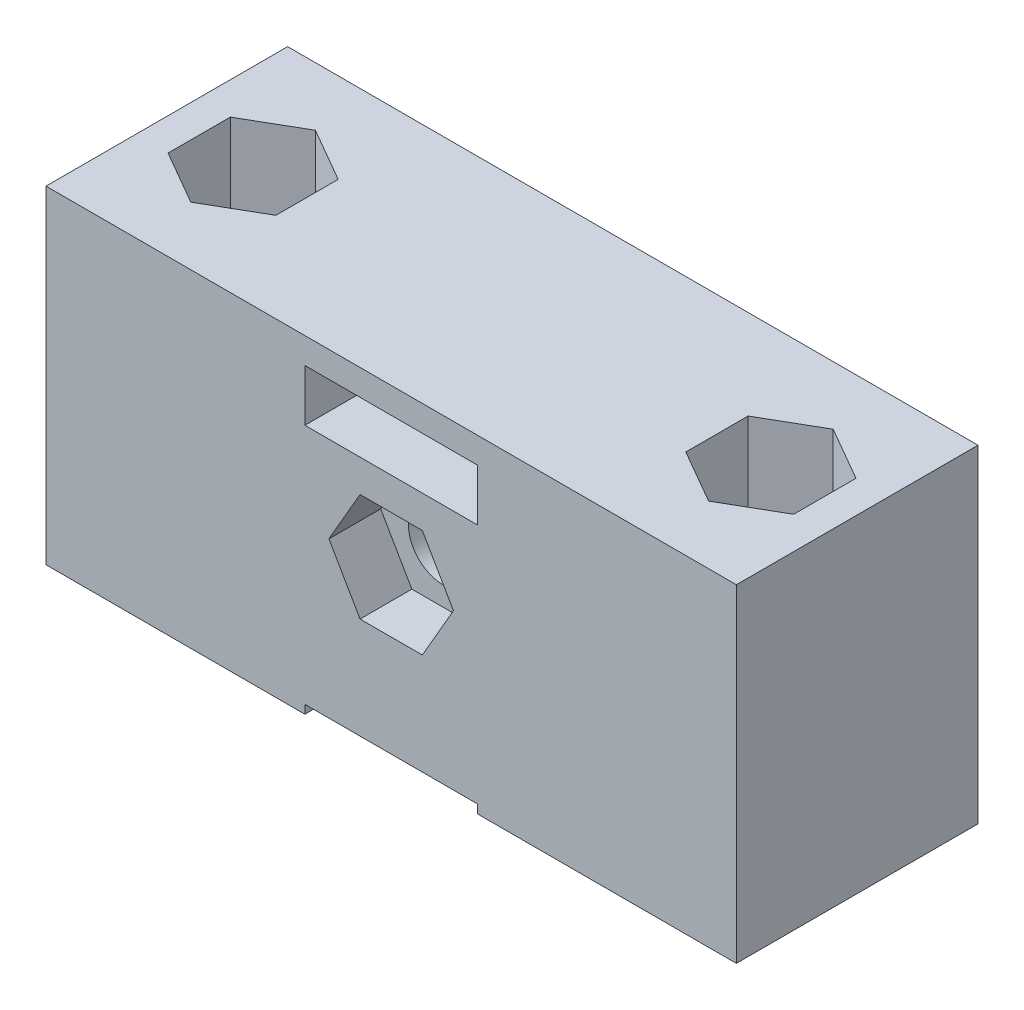
SolidWorks part; units mm, degrees
ref_plane "Front Plane" through (0, 0, 0) normal (0, 0, 1) x (1, 0, 0)
ref_plane "Top Plane" through (0, 0, 0) normal (0, 1, 0) x (1, 0, 0)
ref_plane "Right Plane" through (0, 0, 0) normal (1, 0, 0) x (0, 0, -1)
sketch "Sketch1" plane through (0, 0, 0) normal (0, 1, 0) x (1, 0, 0)
  line L1 (-20, 7) -> (20, 7)
  line L2 (-20, 7) -> (-20, -7)
  line L3 (-20, -7) -> (20, -7)
  line L4 (20, 7) -> (20, -7)
  line L5 (-20, 7) -> (20, -7) construction
  line L6 (-20, -7) -> (20, 7) construction
  point P0 (0, 0)
  dimension "D1" = 40
  dimension "D2" = 14
extrude "Boss-Extrude1" add sketch "Sketch1" along normal blind 19
sketch "Sketch2" plane through (0, 0, 7) normal (0, 0, 1) x (1, 0, 0)
  line L0 (0, 19) -> (0, 0) construction
  line L1 (-20, 19) -> (20, 19) construction
  line L3 (-5, 14.5) -> (5, 14.5)
  line L4 (-5, 14.5) -> (-5, 17.5)
  line L5 (-5, 17.5) -> (5, 17.5)
  line L6 (5, 14.5) -> (5, 17.5)
  line L7 (-5, 14.5) -> (5, 17.5) construction
  line L8 (-5, 17.5) -> (5, 14.5) construction
  line L9 (-5, -0.5) -> (5, -0.5)
  line L10 (-5, -0.5) -> (-5, 0.5)
  line L11 (-5, 0.5) -> (5, 0.5)
  line L12 (5, -0.5) -> (5, 0.5)
  line L13 (-5, -0.5) -> (5, 0.5) construction
  line L14 (-5, 0.5) -> (5, -0.5) construction
  point P5 (0, 16)
  dimension "D1" = 10
  dimension "D2" = 3
  dimension "D3" = 16
  dimension "D4" = 10
  dimension "D5" = 1
extrude "Cut-Extrude1" cut sketch "Sketch2" against normal blind 30
sketch "Sketch3" plane through (0, 0, 7) normal (0, 0, 1) x (1, 0, 0)
  line L0 (0, 19) -> (0, 0) construction
  line L1 (-20, 19) -> (20, 19) construction
  circle A0 centre (0, 9.5) radius 2
  dimension "D1" = 4
extrude "Cut-Extrude2" cut sketch "Sketch3" against normal through all
sketch "Sketch4" plane through (0, 19, 0) normal (0, 1, 0) x (1, 0, 0)
  line L0 (-20, 0) -> (20, 0) construction
  line L1 (-20, 7) -> (-20, -7) construction
  line L2 (20, -7) -> (20, 7) construction
  line L3 (0, 7) -> (0, -7) construction
  line L4 (20, 7) -> (-20, 7) construction
  line L5 (-20, -7) -> (20, -7) construction
  circle A0 centre (-15, 0) radius 1.6
  circle A1 centre (15, 0) radius 1.6
  dimension "D1" = 3.2
  dimension "D2" = 15
extrude "Cut-Extrude3" cut sketch "Sketch4" against normal through all
sketch "Sketch8" plane through (0, 0, 0) normal (0, -1, 0) x (-1, 0, 0)
  line L0 (-5, 7) -> (-5, -7) construction
  line L1 (5, -7) -> (-5, -7)
  line L2 (5, -7) -> (5, -6)
  line L3 (5, -6) -> (-5, -6)
  line L4 (-5, -7) -> (-5, -6)
  dimension "D1" = 1
extrude "Boss-Extrude2" [suppressed] add sketch "Sketch8" against normal up to next
sketch "Sketch9" plane through (0, 19, 0) normal (0, 1, 0) x (1, 0, 0)
  line L0 (0, 7) -> (0, -7) construction
  line L1 (-15, 3.6084) -> (-18.125, 1.8042)
  line L2 (-18.125, 1.8042) -> (-18.125, -1.8042)
  line L3 (-18.125, -1.8042) -> (-15, -3.6084)
  line L4 (-15, -3.6084) -> (-11.875, -1.8042)
  line L5 (-11.875, -1.8042) -> (-11.875, 1.8042)
  line L6 (-11.875, 1.8042) -> (-15, 3.6084)
  line L7 (20, 7) -> (-20, 7) construction
  line L8 (-20, -7) -> (20, -7) construction
  line L9 (11.875, 1.8042) -> (15, 3.6084)
  line L10 (11.875, -1.8042) -> (11.875, 1.8042)
  line L11 (15, -3.6084) -> (11.875, -1.8042)
  line L12 (18.125, -1.8042) -> (15, -3.6084)
  line L13 (18.125, 1.8042) -> (18.125, -1.8042)
  line L14 (15, 3.6084) -> (18.125, 1.8042)
  circle A0 centre (-15, 0) radius 3.125 construction
  circle A1 centre (15, 0) radius 3.125 construction
  dimension "D1" = 6.25
extrude "Cut-Extrude4" cut sketch "Sketch9" against normal blind 10
sketch "Sketch10" plane through (0, 0, 7) normal (0, 0, 1) x (1, 0, 0)
  line L1 (1.8042, 12.625) -> (-1.8042, 12.625)
  line L2 (-1.8042, 12.625) -> (-3.6084, 9.5)
  line L3 (-3.6084, 9.5) -> (-1.8042, 6.375)
  line L4 (-1.8042, 6.375) -> (1.8042, 6.375)
  line L5 (1.8042, 6.375) -> (3.6084, 9.5)
  line L6 (3.6084, 9.5) -> (1.8042, 12.625)
  circle A0 centre (0, 9.5) radius 3.125 construction
  dimension "D1" = 6.25
extrude "Cut-Extrude5" cut sketch "Sketch10" against normal blind 3
equation "\"X-ROD-SPACING\"=45"
equation "\"Y-ROD-SPACING\"=75"
equation "\"Z-ROD-SPACING\"=17.5"
equation "\"Y-BED-OFFSET\"=2"
equation "\"Y-BED-ROD-INSET\"=3.5"
equation "\"Y-BED-SCREW-SPACING\"=209"
equation "\"Y-BED-SCREW-CUTOUT-SLOT-HEIGHT\"=2"
equation "\"T-SLOT-NUT-FILLET-RADIUS\"=0.5"
equation "\"T-SLOT-SCREW-SHAFT-RADIUS\"=1.55"
equation "\"T-SLOT-SCREW-SHAFT-CUTOUT-LENGTH\"=11"
equation "\"T-SLOT-NUT-DEPTH\"=3.5"
equation "\"T-SLOT-NUT-WIDTH\"=2.85"
equation "\"T-SLOT-NUT-END-DISTANCE\"=8"
equation "\"ACRYLIC-THICKNESS\"=10"
equation "\"ACRYLIC-THICKNESS2\"=4.5"
equation "\"ACRYLIC-TAB-CUTOUT-SIZE\"=\"ACRYLIC-THICKNESS\"+\"ACRYLIC-TAB-TOLERANCE\"*2"
equation "\"ACRYLIC-TAB-TOLERANCE\"=-.05"
equation "\"ACRYLIC-TAB-WIDTH\"=\"ACRYLIC-THICKNESS\""
equation "\"ACRYLIC-M3-HOLE\"=2.9"
equation "\"SMOOTHROD-CAP-SCREW-DISTANCE\"=20"
equation "\"FRAME-WIDTH-INNER\"=370"
equation "\"NEMA17-HOLE-SPACING\"=31"
equation "\"NEMA17-CENTRAL-CUTOUT\"=22.5"
equation "\"Z-BRACKET-REACH\"=57"
equation "\"Z-ROD-INSET\"=13.5"
equation "\"TOP-BRACKET-SPACING\"=40"
equation "\"SMOOTHROD-X-LENGTH\"=350"
equation "\"SMOOTHROD-Y-LENGTH\"=350"
equation "\"SMOOTHROD-Z-LENGTH\"=350"
equation "\"SMOOTHROD-TIGHTENING-HEADROOM\"=.25"
equation "\"LEADSCREW-Z-LENGTH\"=300"
equation "\"SCREW-LENGTH-FRAME\"=\"ACRYLIC-THICKNESS\" + 10"
equation "\"SCREW-LENGTH-MOTOR\"=\"ACRYLIC-THICKNESS\" + 5"
equation "\"SCREW-LENGTH-EXTRUDER\"=28"
equation "\"SCREW-HEAD-RADIUS\"=6"
equation "\"PRINTED-M3-HOLE\"=3.5"
equation "\"PRINTED-X-SMOOTHROD-DIAMETER\"=8.8"
equation "\"PRINTED-X-SMOOTHROD-CUTOUT\"=10"
equation "\"PRINTED-X-BASE-HEIGHT\"=10"
equation "\"PRINTED-LM8UU-CUTOUT-SIZE\"=15.5"
equation "\"PRINTED-LM8UU-CUTOUT-LENGTH\"=24.5"
equation "\"PRINTED-X-IDLER-HEIGHT\"=16"
equation "\"PSU-MOUNTING-WIDTH\"=95"
equation "\"PSU-MOUNTING-HEIGHT\"=177"
equation "\"Y-BELT-TO-ROD-DISTANCE\"=20"
equation "\"SPOOL-HOLDER-ROD-SPACING\"=150"
equation "\"ACRYLIC-X-CARRIAGE-WIDTH\"=55"
equation "\"ACRYLIC-X-CARRIAGE-HEIGHT\"=75"
equation "\"ACRYLIC-X-CARRIAGE-LM8UU-CUTOUT-WIDTH\"=24.25"
equation "\"ACRYLIC-X-CARRIAGE-LM8UU-CUTOUT-HEIGHT\"=11.0"
equation "\"ACRYLIC-X-CARRIAGE-SCREW-SPACING-X\"=15"
equation "\"ACRYLIC-X-CARRIAGE-SCREW-SPACING-Y\"=33"
equation "\"ACRYLIC-X-CARRIAGE-CENTER-TAB-SPACING\"=14"
equation "\"ACRYLIC-X-CARRIAGE-EXTRUDER-OFFSET\"=26"
equation "\"ACRYLIC-X-CARRIAGE-EXTRUDER-ANGLE\"=90"
equation "\"ACRYLIC-X-CARRIAGE-EXTRUDER-SHELF-DEPTH\"=\"ACRYLIC-X-CARRIAGE-EXTRUDER-OFFSET\" + 28"
equation "\"ACRYLIC-X-CARRIAGE-EXTRUDER-BRACE-SPACING\"=23"
equation "\"ACRYLIC-X-CARRIAGE-EXTRUDER-BRACE-TAB-OFFSET\"=20"
equation "\"ACRYLIC-X-CARRIAGE-EXTRUDER-BRACE-HEIGHT\"=35"
equation "\"ACRYLIC-X-CARRIAGE-EXTRUDER-BRACE-SCREW-SPACING\"=22"
equation "\"ACRYLIC-X-CARRIAGE-DUAL-WIDTH-MULTIPLIER\"=1.65"
equation "\"ACRYLIC-X-CARRIAGE-DUAL-HOTEND-SPACING\"=42"
equation "\"ACRYLIC-X-CARRIAGE-DUAL-WIDTH\"=75"
equation "\"ACRYLIC-X-CARRIAGE-DUAL-HOTEND-SEPARATION\"=36"
equation "\"ACRYLIC-X-CARRIAGE-DUAL-MOUNT-PLATE-DEPTH\"=75"
equation "\"ACRYLIC-X-CARRIAGE-DUAL-MOUNT-BRACE-WIDTH\"=33"
equation "\"ACRYLIC-X-CARRIAGE-DUAL-MOUNT-SCREW-WIDTH\"=40"
equation "\"BLOWER-FAN-WIDTH\"=15"
equation "\"PRINTED-M3-NUT-AF\"=6.25"
equation "\"D1@Sketch9\"=\"PRINTED-M3-NUT-AF\""
equation "\"D1@Sketch10\"=\"PRINTED-M3-NUT-AF\""
